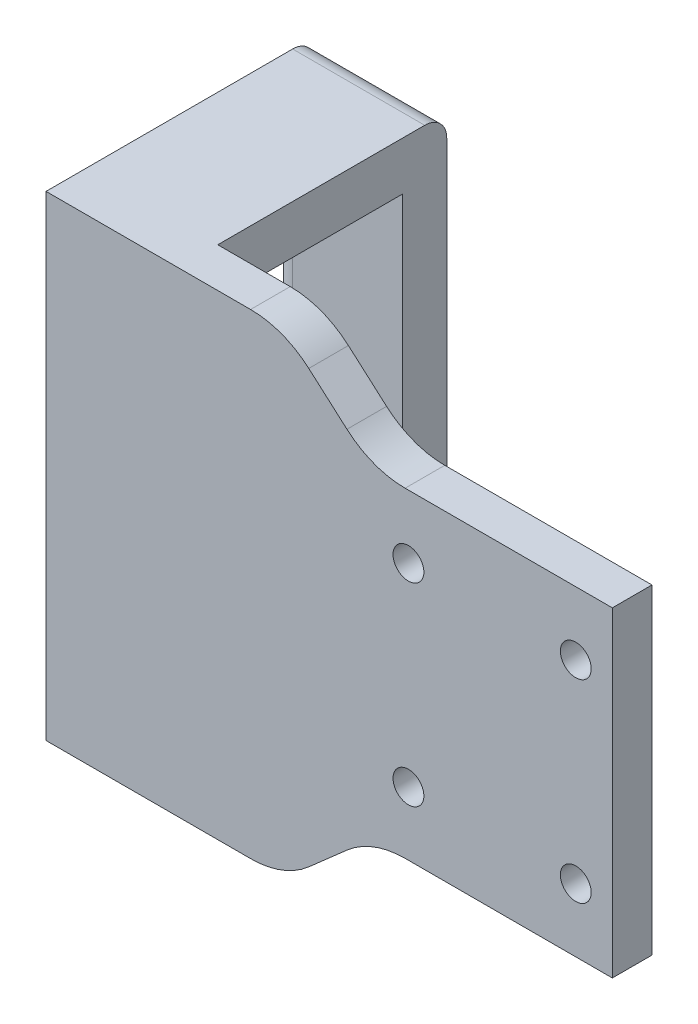
SolidWorks part; units mm, degrees
ref_plane "Front Plane" through (0, 0, 0) normal (0, 0, 1) x (1, 0, 0)
ref_plane "Top Plane" through (0, 0, 0) normal (0, 1, 0) x (1, 0, 0)
ref_plane "Right Plane" through (0, 0, 0) normal (1, 0, 0) x (0, 0, -1)
sketch "Sketch1" plane through (0, 0, 0) normal (0, 0, 1) x (1, 0, 0)
  line L0 (0, 18.2) -> (0, -18.2) construction
  line L1 (-13.65, -18.2) -> (13.65, -18.2)
  line L2 (-13.65, -18.2) -> (-13.65, 18.2) construction
  line L3 (-13.65, 18.2) -> (13.65, 18.2)
  line L4 (13.65, -18.2) -> (13.65, 18.2)
  line L5 (-13.65, -18.2) -> (13.65, 18.2) construction
  line L6 (-13.65, 18.2) -> (13.65, -18.2) construction
  line L7 (-13.65, 0) -> (13.65, 0) construction
  line L8 (-13.65, 0) -> (-113.65, 0) construction
  line L9 (-13.65, 18.2) -> (-23.65, 27)
  line L10 (-23.65, 27) -> (-50.65, 27)
  line L11 (-23.65, 27) -> (-23.65, -27) construction
  line L12 (-23.65, -27) -> (-50.65, -27)
  line L13 (-50.65, 27) -> (-50.65, -27)
  line L14 (-23.65, 27) -> (-50.65, -27) construction
  line L15 (-23.65, -27) -> (-50.65, 27) construction
  line L17 (-13.65, -18.2) -> (-23.65, -27)
  circle A0 centre (-9.5, 11) radius 1.75
  circle A1 centre (9.5, 11) radius 1.75
  circle A2 centre (-9.5, -11) radius 1.75
  circle A3 centre (9.5, -11) radius 1.75
  point P0 (0, 0)
  point P18 (-37.15, 0)
  dimension "D3" = 3.5
  dimension "D4" = 11
  dimension "D5" = 9.5
  dimension "D1" = 36.4
  dimension "D2" = 27.3
  dimension "D6" = 100
  dimension "D7" = 54
  dimension "D8" = 27
  dimension "D9" = 10
extrude "Boss-Extrude1" add sketch "Sketch1" along normal blind 4.5
sketch "Sketch2" plane through (0, 0, 0) normal (0, 0, -1) x (-1, 0, 0)
  line L0 (50.65, -27) -> (23.65, -27) construction
  line L1 (50.65, 27) -> (35.65, 27)
  line L2 (50.65, 27) -> (50.65, -27)
  line L3 (50.65, -27) -> (35.65, -27)
  line L4 (35.65, 27) -> (35.65, -27)
  dimension "D1" = 15
extrude "Boss-Extrude2" add sketch "Sketch2" along normal blind 26
sketch "Sketch5" plane through (-35.65, 0, 0) normal (1, 0, 0) x (0, 0, -1)
  line L0 (0, 0) -> (50000, 0) construction
  line L1 (0, 27) -> (0, -27) construction
  line L2 (21, -21.5) -> (0, -21.5)
  line L3 (21, -21.5) -> (21, 21.5)
  line L4 (21, 21.5) -> (0, 21.5)
  line L5 (0, -21.5) -> (0, 21.5)
  line L6 (21, -21.5) -> (0, 21.5) construction
  line L7 (21, 21.5) -> (0, -21.5) construction
  point P3 (10.5, 0)
  dimension "D1" = 43
  dimension "D2" = 21
extrude "Cut-Extrude1" cut sketch "Sketch5" against normal up to surface (15 mm away) up to face at (-50.65, 0, -10.75)
sketch "Sketch6" plane through (-50.65, 0, 0) normal (-1, 0, 0) x (0, 0, 1)
  line L0 (-10.5, 21.5) -> (-10.5, -21.5) construction
  line L1 (0, 21.5) -> (-21, 21.5) construction
  line L2 (-21, -21.5) -> (0, -21.5) construction
  line L3 (-21, 0) -> (0, 0) construction
  line L4 (-21, 21.5) -> (-21, -21.5) construction
  line L5 (0, -21.5) -> (0, 21.5) construction
  circle A0 centre (-15.5, 24.75) radius 1.35
  circle A1 centre (-5.5, 24.75) radius 1.35
  circle A2 centre (-5.5, -24.75) radius 1.35
  circle A3 centre (-15.5, -24.75) radius 1.35
  dimension "D1" = 2.7
  dimension "D2" = 5
  dimension "D3" = 24.75
ref_plane "Plane1" through (0, 0, -10.5) normal (0, 0, -1) x (-1, 0, 0)
ref_plane "Plane2" through (0, 0, 0) normal (0, 1, 0) x (1, 0, 0)
extrude "Cut-Extrude2" cut sketch "Sketch6" against normal blind 12
sketch "Sketch8" plane through (-50.65, 0, 0) normal (-1, 0, 0) x (0, 0, 1)
  line L3 (-15.5, -21.5) -> (-5.5, -21.5)
  line L4 (-21, -21.5) -> (0, -21.5) construction
  line L5 (-15.5, -23.75) -> (-5.5, -23.75) construction
  line L6 (-15.5, -21.5) -> (-15.5, -23.75) construction
  line L7 (-5.5, -23.75) -> (-5.5, -21.5) construction
  arc A1 (-15.5, -21.5) -> (-5.5, -21.5) centre (-10.5, -17.0694) ccw
  point P5 (-10.5, -21.5)
  dimension "D1" = 10
  dimension "D2" = 2.25
extrude "Cut-Extrude3" cut sketch "Sketch8" against normal up to surface (15 mm away) up to face at (-35.65, 0, -11.75)
fillet "Fillet1" radius 10 4 edges at (-23.65, -27, 2.25) (-23.65, 27, 2.25) (-13.65, -18.2, 2.25) (-13.65, 18.2, 2.25)
fillet "Fillet3" radius 2.5 4 edges at (-43.15, 27, -26) (-43.15, -27, -26) (-50.65, 0, -21) (-50.65, 0, 0)
